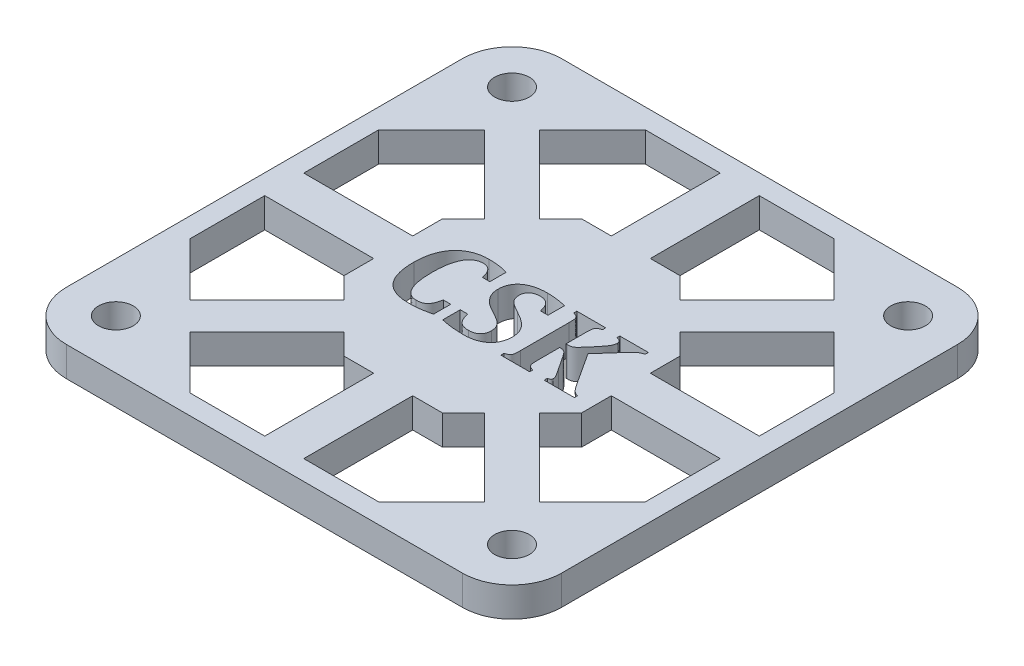
SolidWorks part; units mm, degrees
ref_plane "Front Plane" through (0, 0, 0) normal (0, 0, 1) x (1, 0, 0)
ref_plane "Top Plane" through (0, 0, 0) normal (0, 1, 0) x (1, 0, 0)
ref_plane "Right Plane" through (0, 0, 0) normal (1, 0, 0) x (0, 0, -1)
sketch "Sketch1" plane through (0, 0, 0) normal (0, 1, 0) x (1, 0, 0)
  line L1 (0, 0) -> (50, 0)
  line L2 (0, 0) -> (0, 50)
  line L3 (0, 50) -> (50, 50)
  line L4 (50, 0) -> (50, 50)
  dimension "D1" = 50
extrude "Boss-Extrude1" add sketch "Sketch1" along normal blind 3
sketch "Sketch2" plane through (0, 3, 0) normal (0, 1, 0) x (1, 0, 0)
  line L0 (5, 45) -> (45, 5) construction
  line L1 (5, 5) -> (45, 45) construction
  line L2 (25, 0) -> (25, 50) construction
  line L3 (0, 0) -> (50, 0) construction
  line L4 (50, 50) -> (0, 50) construction
  circle A0 centre (5, 5) radius 1.75
  circle A1 centre (45, 5) radius 1.75
  circle A2 centre (45, 45) radius 1.75
  circle A3 centre (5, 45) radius 1.75
  point P8 (25, 25)
  dimension "D1" = 3.5
  dimension "D2" = 40
extrude "Cut-Extrude1" cut sketch "Sketch2" against normal through all
fillet "Fillet1" radius 5 4 edges at (50, 1.5, -50) (0, 1.5, -50) (50, 1.5, 0) (0, 1.5, 0)
sketch "Sketch4" plane through (0, 3, 0) normal (0, 1, 0) x (1, 0, 0)
  line L0 (25, 50) -> (25, 0) construction
  line L1 (45, 50) -> (5, 50) construction
  line L2 (5, 0) -> (45, 0) construction
  line L3 (0, 25) -> (50, 25) construction
  line L4 (0, 45) -> (0, 5) construction
  line L5 (50, 5) -> (50, 45) construction
  line L6 (48, 34.5269) -> (34.5269, 48) construction
  line L7 (37, 29.9706) -> (29.9706, 37) construction
  line L8 (29.9706, 37) -> (20.0294, 37) construction
  line L9 (20.0294, 37) -> (13, 29.9706) construction
  line L10 (13, 29.9706) -> (13, 20.0294) construction
  line L11 (13, 20.0294) -> (20.0294, 13) construction
  line L12 (20.0294, 13) -> (29.9706, 13) construction
  line L13 (29.9706, 13) -> (37, 20.0294) construction
  line L14 (37, 20.0294) -> (37, 29.9706) construction
  line L15 (34.5269, 48) -> (15.4731, 48) construction
  line L16 (15.4731, 48) -> (2, 34.5269) construction
  line L17 (2, 34.5269) -> (2, 15.4731) construction
  line L18 (2, 15.4731) -> (15.4731, 2) construction
  line L19 (15.4731, 2) -> (34.5269, 2) construction
  line L20 (34.5269, 2) -> (48, 15.4731) construction
  line L21 (48, 15.4731) -> (48, 34.5269) construction
  line L22 (32.0919, 34.8787) -> (39.8701, 42.6569)
  line L23 (26.9706, 37) -> (26.9706, 48)
  line L24 (32.0919, 34.8787) -> (29.9706, 37)
  line L25 (29.9706, 37) -> (26.9706, 37)
  line L26 (39.8701, 42.6569) -> (34.5269, 48)
  line L27 (34.5269, 48) -> (26.9706, 48)
  circle A0 centre (25, 25) radius 12 construction
  dimension "D1" = 24
  dimension "D3" = 3
  dimension "D4" = 3
  dimension "D2" = 11
extrude "Cut-Extrude2" cut sketch "Sketch4" against normal through all
ref_plane "Plane1" through (0, 0, -25) normal (0, 0, 1) x (1, 0, 0)
ref_plane "Plane2" through (25, 0, 0) normal (1, 0, 0) x (0, 0, -1)
ref_axis "Axis1" through (25, 3.15, -25) along (0, -1, 0)
pattern_circular "CirPattern1" count 8 over 360 about axis through (25, 3.15, -25) along (0, -1, 0) of "Cut-Extrude2"
sketch "Sketch5" plane through (0, 3, 0) normal (0, 1, 0) x (1, 0, 0)
  line L0 (13, 21) -> (37, 21) construction
  line L1 (13, 20.0294) -> (13, 23.0294) construction
  line L2 (37, 23.0294) -> (37, 20.0294) construction
  line L3 (23.0294, 13) -> (20.0294, 13) construction
  text T0 "CSK" font "Cambria" height in points 28
  dimension "D1" = 8
extrude "Cut-Extrude3" cut sketch "Sketch5" against normal through all
